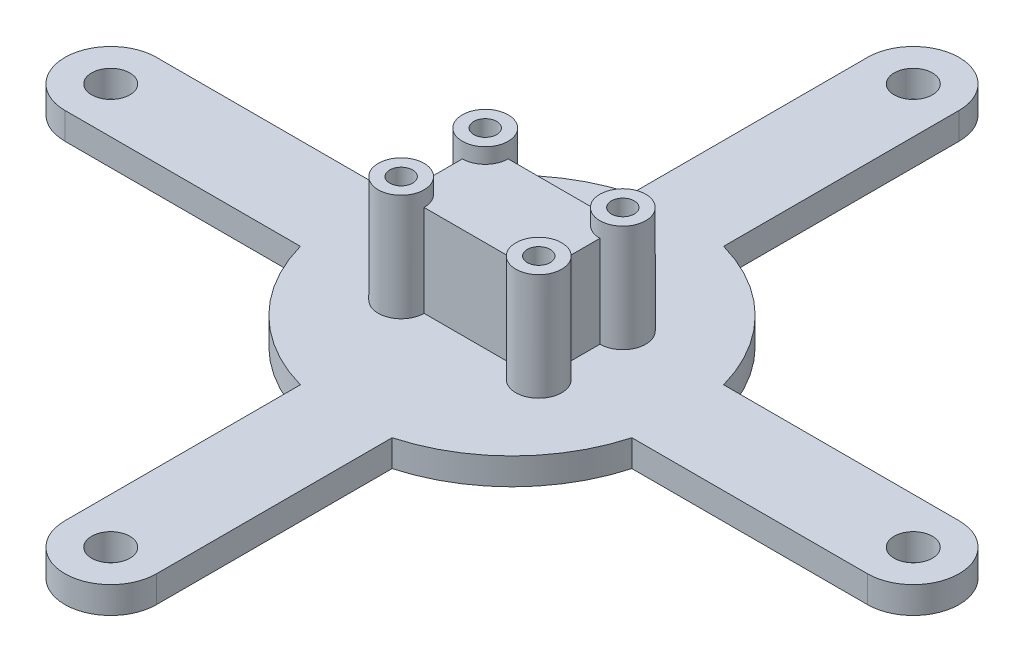
SolidWorks part; units mm, degrees
ref_plane "Front Plane" through (0, 0, 0) normal (0, 0, 1) x (1, 0, 0)
ref_plane "Top Plane" through (0, 0, 0) normal (0, 1, 0) x (1, 0, 0)
ref_plane "Right Plane" through (0, 0, 0) normal (1, 0, 0) x (0, 0, -1)
sketch "Sketch1" plane through (0, 0, 0) normal (0, 1, 0) x (1, 0, 0)
  line L0 (-52.5, 6) -> (-21.6852, 6)
  line L1 (-52.5, -6) -> (-21.6852, -6)
  line L2 (-6, 52.5) -> (-6, 21.6852)
  line L3 (6, 52.5) -> (6, 21.6852)
  line L4 (21.6852, 6) -> (52.5, 6)
  line L5 (-6, -21.6852) -> (-6, -52.5)
  line L6 (21.6852, -6) -> (52.5, -6)
  line L7 (6, -21.6852) -> (6, -52.5)
  circle A0 centre (0, 0) radius 52.5 construction
  circle A1 centre (-52.5, 0) radius 2.5
  circle A2 centre (0, 52.5) radius 2.5
  circle A3 centre (52.5, 0) radius 2.5
  circle A4 centre (0, -52.5) radius 2.5
  arc A5 (-52.1571, 5.9902) -> (-52.1571, -5.9902) centre (-52.5, 0) ccw
  arc A6 (5.9902, 52.1571) -> (-5.9902, 52.1571) centre (0, 52.5) ccw
  arc A7 (52.1571, -5.9902) -> (52.1571, 5.9902) centre (52.5, 0) ccw
  arc A8 (-5.9902, -52.1571) -> (5.9902, -52.1571) centre (0, -52.5) ccw
  arc A9 (-21.6852, -6) -> (-6, -21.6852) centre (0, 0) ccw
  arc A10 (-6, 21.6852) -> (-21.6852, 6) centre (0, 0) ccw
  arc A11 (21.6852, 6) -> (6, 21.6852) centre (0, 0) ccw
  arc A12 (6, -21.6852) -> (21.6852, -6) centre (0, 0) ccw
  point P14 (0, 0)
  point P22 (0, 0)
  dimension "D1" = 105
  dimension "D2" = 5
  dimension "D4" = 12
  dimension "D6" = 45
  dimension "D3" = 4
  dimension "D5" = 4
extrude "Boss-Extrude1" add sketch "Sketch1" along normal blind 3.5 contours L7 A12 L6 A7 L4 A11 L3 A6 L2 A10 L0 A5 L1 A9 L5 A8 A1 A2 A3 A4 region at (0, 0, 0)
sketch "Sketch3" plane through (0, 3.5, 0) normal (0, 1, 0) x (1, 0, 0)
  circle A0 centre (0, 0) radius 2.5
  dimension "D1" = 5
sketch "Sketch4" plane through (0, 3.5, 0) normal (0, 1, 0) x (1, 0, 0)
  line L3 (-6, -5.5) -> (6, -5.5)
  line L5 (9, -2.5) -> (9, 2.5)
  line L7 (6, 5.5) -> (-6, 5.5)
  line L9 (-9, 2.5) -> (-9, -2.5)
  circle A0 centre (9, -5.5) radius 1.5
  circle A1 centre (-9, -5.5) radius 1.5
  circle A2 centre (-9, 5.5) radius 1.5
  circle A3 centre (9, 5.5) radius 1.5
  arc A4 (6, -5.5) -> (9, -2.5) centre (9, -5.5) ccw
  arc A5 (9, 2.5) -> (6, 5.5) centre (9, 5.5) ccw
  arc A6 (-6, 5.5) -> (-9, 2.5) centre (-9, 5.5) ccw
  arc A7 (-9, -2.5) -> (-6, -5.5) centre (-9, -5.5) ccw
  dimension "D3" = 3
  dimension "D6" = 3
  dimension "D7" = 3
  dimension "D12" = 3
  dimension "D13" = 6
  dimension "D14" = 6
  dimension "D15" = 6
  dimension "D16" = 6
  dimension "D1" = 9
  dimension "D2" = 5.5
  dimension "D4" = 9
  dimension "D5" = 5.5
  dimension "D8" = 18
  dimension "D9" = 11
  dimension "D10" = 11
  dimension "D11" = 18
extrude "Boss-Extrude2" add sketch "Sketch4" along normal blind 14
sketch "Sketch6" plane through (0, 17.5, 0) normal (0, 1, 0) x (1, 0, 0)
  line L30 (6, 5.5) -> (-6, 5.5)
  line L31 (-9, 2.5) -> (-9, -2.5)
  line L32 (-6, -5.5) -> (6, -5.5)
  line L33 (9, -2.5) -> (9, 2.5)
  line L34 (6, 5.5) -> (-6, 5.5)
  line L35 (-9, 2.5) -> (-9, -2.5)
  line L36 (-6, -5.5) -> (6, -5.5)
  line L37 (9, -2.5) -> (9, 2.5)
  arc A0 (6, 5.5) -> (9, 2.5) centre (9, 5.5) ccw
  arc A1 (9, -2.5) -> (6, -5.5) centre (9, -5.5) ccw
  arc A2 (-6, -5.5) -> (-9, -2.5) centre (-9, -5.5) ccw
  arc A3 (-9, 2.5) -> (-6.1311, 6.3771) centre (-9, 5.5) ccw
  arc A4 (9, 2.5) -> (6, 5.5) centre (9, 5.5) ccw
  arc A5 (-6, 5.5) -> (-9, 2.5) centre (-9, 5.5) ccw
  arc A6 (-9, -2.5) -> (-6, -5.5) centre (-9, -5.5) ccw
  arc A7 (6, -5.5) -> (9, -2.5) centre (9, -5.5) ccw
  arc A9 (-6, 5.5) -> (-6.1311, 6.3771) centre (-9, 5.5) ccw
  dimension "D1" = 0
extrude "Cut-Extrude4" cut sketch "Sketch6" against normal blind 2 contours A3 L33 A2 A1 A4 A0 L31 region at (0, 17.5, 0)
extrude "Cut-Extrude2" cut sketch "Sketch4<2>" against normal blind 10 contours A1 | A0 | A2 | A3 region at (-9, 3.5, 5.5)
sketch "Sketch4<2>" plane through (0, 3.5, 0) normal (0, 1, 0) x (1, 0, 0) same geometry as "Sketch4"
